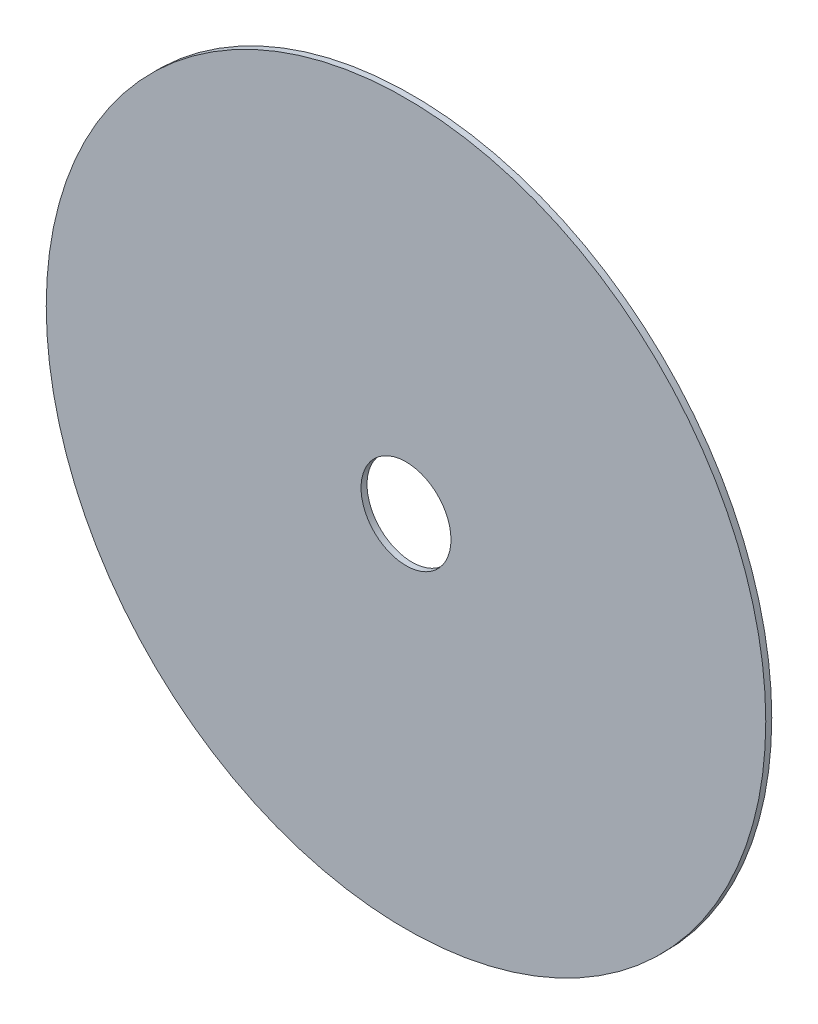
SolidWorks part; units mm, degrees
ref_plane "Plan de face" through (0, 0, 0) normal (0, 0, 1) x (1, 0, 0)
ref_plane "Plan de dessus" through (0, 0, 0) normal (0, 1, 0) x (1, 0, 0)
ref_plane "Plan de droite" through (0, 0, 0) normal (1, 0, 0) x (0, 0, -1)
sketch "Esquisse1" plane through (0, 0, 0) normal (0, 0, 1) x (1, 0, 0)
  circle A0 centre (0, 0) radius 7.5
  circle A1 centre (0, 0) radius 58
  circle A2 centre (0, 0) radius 60
  circle A3 centre (0, 0) radius 23
  circle A5 centre (0, 0) radius 25
  dimension "D1" = 120
  dimension "D2" = 116
  dimension "D3" = 15
  dimension "D4" = 50
  dimension "D5" = 46
extrude "Boss.-Extru.1" add sketch "Esquisse1" along normal blind 1 contours A1 A5 | A2 A1 | A5 A3 | A3 A0 region at (-56.3595, 0, 0) region at (-58.3029, 0, 0) region at (-22.3495, 0, 0) region at (-24.2929, 0, 0)
